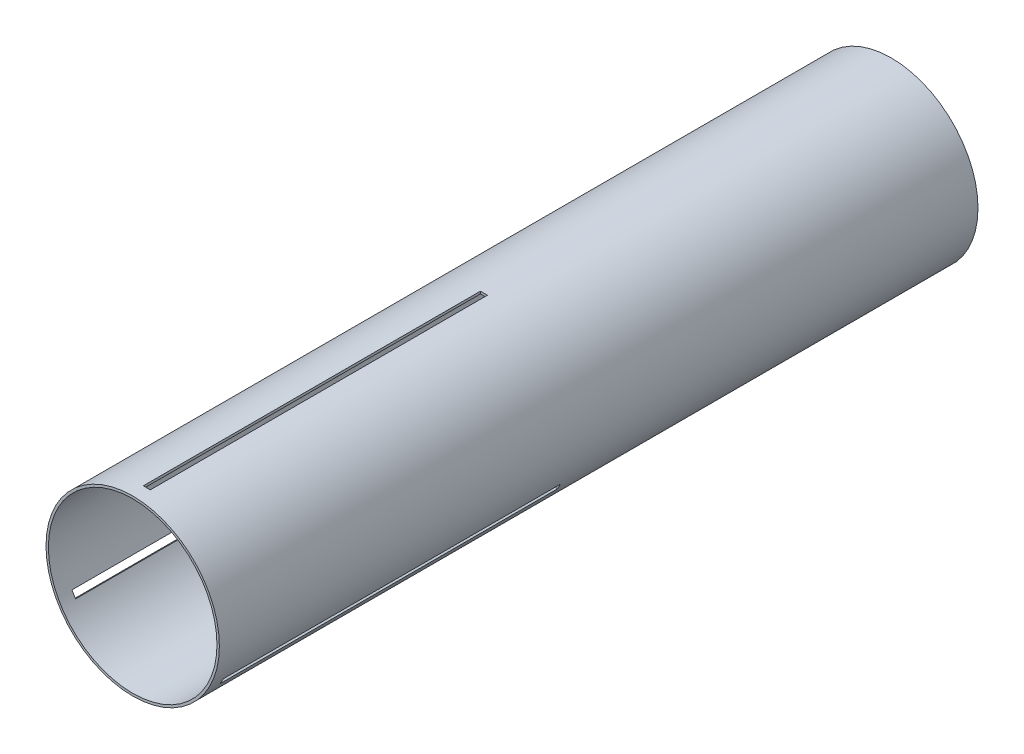
SolidWorks part; units mm, degrees
ref_plane "Plan de face" through (0, 0, 0) normal (0, 0, 1) x (1, 0, 0)
ref_plane "Plan de dessus" through (0, 0, 0) normal (0, 1, 0) x (1, 0, 0)
ref_plane "Plan de droite" through (0, 0, 0) normal (1, 0, 0) x (0, 0, -1)
sketch "Esquisse2" plane through (0, 0, 0) normal (0, 0, 1) x (1, 0, 0)
  circle A0 centre (0, 0) radius 78.359
  circle A1 centre (0, 0) radius 76.2
  dimension "D1" = 156.718
  dimension "D2" = 152.4
extrude "Boss.-Extru.1" add sketch "Esquisse2" along normal blind 685.8
sketch "Esquisse3" plane through (0, 0, 0) normal (0, 1, 0) x (1, 0, 0)
  line L0 (0, -685.8) -> (0, -673.1)
  line L1 (-78.359, -685.8) -> (78.359, -685.8) construction
  line L2 (0, -673.1) -> (0, -520.7)
  line L3 (0, -673.1) -> (-3.175, -673.1)
  line L5 (3.175, -368.3) -> (-3.175, -368.3)
  line L6 (3.175, -368.3) -> (3.175, -673.1)
  line L7 (3.175, -673.1) -> (-3.175, -673.1)
  line L8 (-3.175, -368.3) -> (-3.175, -673.1)
  line L9 (3.175, -368.3) -> (-3.175, -673.1) construction
  line L10 (3.175, -673.1) -> (-3.175, -368.3) construction
  dimension "D1" = 12.7
  dimension "D2" = 152.4
  dimension "D3" = 3.175
extrude "Enlèv. mat.-Extru.1" cut sketch "Esquisse3" along normal blind 152.4 contours L7 L6 L5 L8
pattern_circular "Répétition circulaire1" count 3 every 120 about axis through (0, 0, 685.8) along (0, 0, -1) of "Enlèv. mat.-Extru.1"
